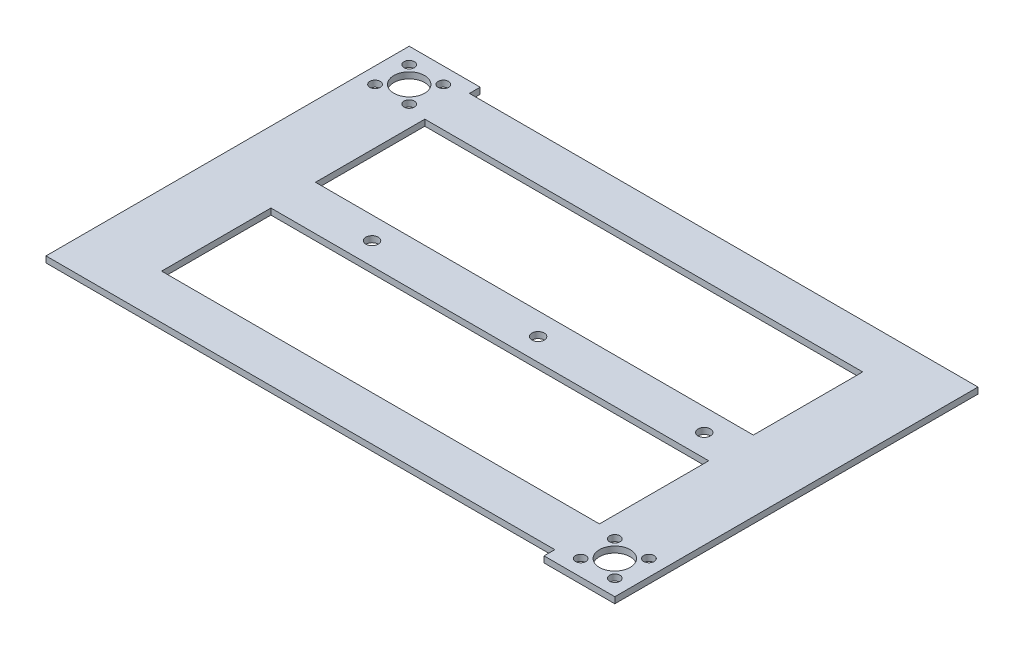
SolidWorks part; units mm, degrees
ref_plane "Front Plane" through (0, 0, 0) normal (0, 0, 1) x (1, 0, 0)
ref_plane "Top Plane" through (0, 0, 0) normal (0, 1, 0) x (1, 0, 0)
ref_plane "Right Plane" through (0, 0, 0) normal (1, 0, 0) x (0, 0, -1)
sketch "Sketch1" plane through (0, 0, 0) normal (0, 1, 0) x (1, 0, 0)
  line L0 (-95.0509, 92.8338) -> (57.8211, 92.8338) construction
  line L1 (-91.977, 142.8838) -> (-86.977, 142.8838) construction
  line L2 (-86.977, 142.8838) -> (-91.977, 142.8838) construction
  line L3 (67.7305, 150.1338) -> (82.2305, 150.1338)
  line L4 (-99.227, 35.5316) -> (-84.727, 35.5316)
  line L5 (-84.727, 35.5316) -> (62.7305, 35.5316)
  line L6 (-79.6432, 50.0316) -> (62.7305, 50.0316)
  line L7 (-79.6432, 150.1338) -> (67.7305, 150.1338)
  line L8 (-79.6432, 135.6338) -> (62.7305, 135.6338)
  line L9 (-79.6432, 100.0827) -> (62.7305, 100.0827)
  line L10 (-79.6432, 85.5827) -> (62.7305, 85.5827)
  line L17 (-84.6432, 153.6338) -> (-79.6432, 153.6338)
  line L18 (-84.6432, 153.6338) -> (-102.727, 153.6338)
  line L19 (-102.727, 100.0827) -> (-102.727, 153.6338)
  line L20 (-79.6432, 153.4321) -> (-79.6432, 150.1338)
  line L21 (-79.6432, 135.6338) -> (-79.6432, 100.0827)
  line L22 (-79.6432, 85.5827) -> (-79.6432, 50.0316)
  line L23 (-102.727, 85.5827) -> (-102.727, 35.5316)
  line L24 (-102.727, 35.5316) -> (-99.227, 35.5316)
  line L25 (67.7305, 32.0316) -> (62.7305, 32.0316)
  line L26 (67.7305, 32.0316) -> (85.7305, 32.0316)
  line L27 (85.7305, 50.0316) -> (85.7305, 32.0316)
  line L28 (62.7305, 32.0316) -> (62.7305, 35.5316)
  line L29 (62.7305, 50.0316) -> (62.7305, 85.5827)
  line L30 (62.7305, 100.0827) -> (62.7305, 135.6338)
  line L31 (85.7305, 50.0316) -> (85.7305, 85.5827)
  line L32 (85.7305, 100.0827) -> (85.7305, 150.1338)
  line L33 (85.7305, 150.1338) -> (82.2305, 150.1338)
  line L34 (-79.6432, 153.4321) -> (-79.6432, 153.6338)
  line L35 (0, -55) -> (0, 55) construction
  line L36 (-102.727, 100.0827) -> (-102.727, 85.5827)
  line L37 (85.7305, 100.0827) -> (85.7305, 85.5827)
  circle A0 centre (-91.977, 142.8838) radius 5
  circle A1 centre (74.9805, 42.7816) radius 5
  circle A2 centre (-86.427, 148.4338) radius 1.7
  circle A3 centre (-97.527, 148.4338) radius 1.7
  circle A4 centre (-86.427, 137.3338) radius 1.7
  circle A5 centre (-97.527, 137.3338) radius 1.7
  circle A6 centre (69.4305, 48.3316) radius 1.7
  circle A7 centre (80.5305, 48.3316) radius 1.7
  circle A8 centre (80.5305, 37.2316) radius 1.7
  circle A9 centre (69.4305, 37.2316) radius 1.7
  circle A10 centre (-54, 92.8338) radius 2
  circle A11 centre (0, 92.8338) radius 2
  circle A13 centre (54, 92.8338) radius 2
  point P38 (0, 0)
  dimension "D1" = 3.4
  dimension "D2" = 3.4
  dimension "D5" = 4
  dimension "D6" = 4
  dimension "D7" = 4
  dimension "D8" = 54
  dimension "D3" = 5
  dimension "D4" = 5
  dimension "D9" = 54
  dimension "D10" = 0
extrude "Boss-Extrude1" add sketch "Sketch1" along normal blind 2
